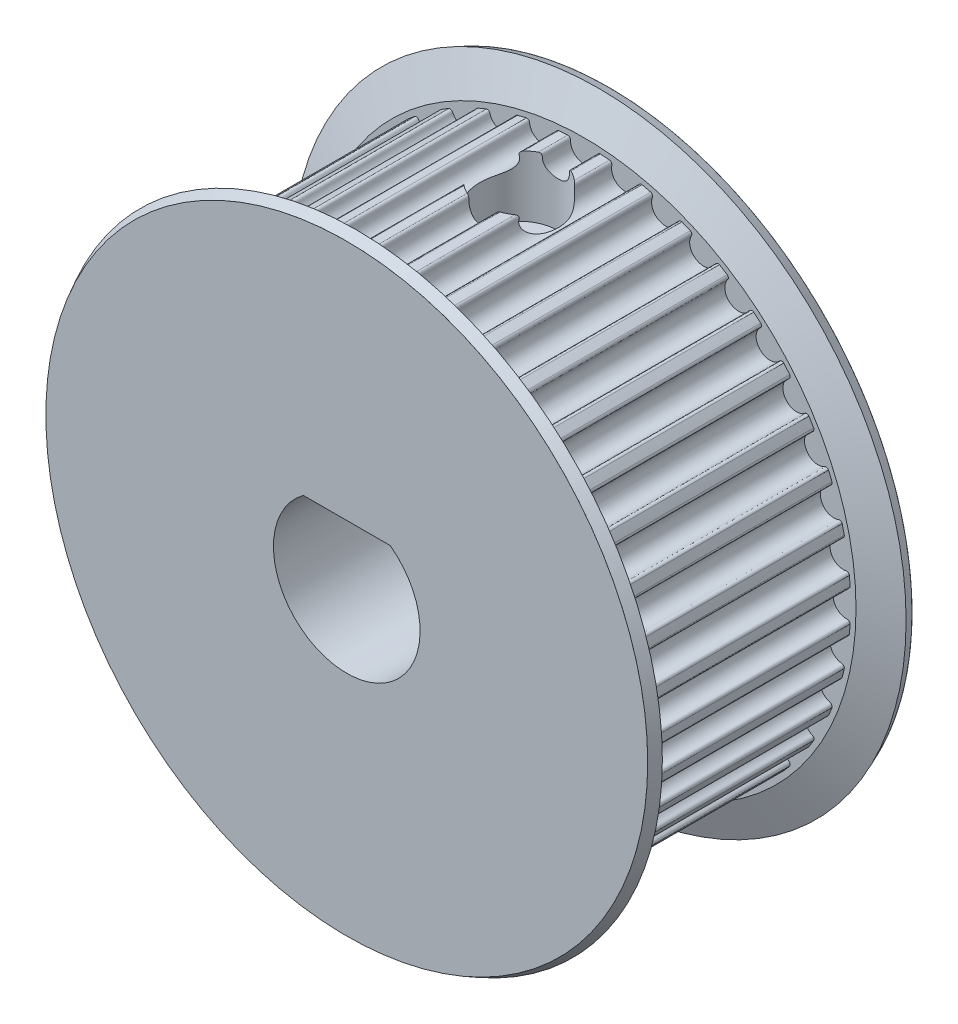
SolidWorks part; units mm, degrees
ref_plane "前视基准面" through (0, 0, 0) normal (0, 0, 1) x (1, 0, 0)
ref_plane "上视基准面" through (0, 0, 0) normal (0, 1, 0) x (1, 0, 0)
ref_plane "右视基准面" through (0, 0, 0) normal (1, 0, 0) x (0, 0, -1)
ref_axis "基准轴1" through (0, 0, 55) along (0, 0, -1)
sketch "SketchRevolveGearBelt01" plane through (0, 0, 0) normal (1, 0, 0) x (0, 0, -1)
  line L0 (0, 0) -> (1, 0) construction
  line L1 (6.4841, 0) -> (6.4841, 19.0696)
  line L2 (6.4841, 19.0696) -> (5.7191, 19.0696)
  line L3 (5.7191, 19.0696) -> (5.7191, 19.934)
  line L4 (5.7191, 19.934) -> (6.2818, 21.2926)
  line L5 (6.2818, 21.2926) -> (5.5778, 21.5842)
  line L6 (5.5778, 21.5842) -> (4.5477, 19.0972)
  line L7 (4.5477, 19.0972) -> (4.5477, 18.7162)
  line L8 (4.5477, 18.7162) -> (-10.2059, 18.7162)
  line L9 (-10.2059, 18.7162) -> (-10.2059, 19.0972)
  line L10 (-10.2059, 19.0972) -> (-11.4448, 21.4871)
  line L11 (-11.4448, 21.4871) -> (-12.1213, 21.1364)
  line L12 (-12.1213, 21.1364) -> (-11.5585, 20.0508)
  line L13 (-11.5585, 20.0508) -> (-11.5585, 19.1864)
  line L14 (-11.5585, 19.1864) -> (-12.3235, 19.1864)
  line L15 (-12.3235, 19.1864) -> (-12.3235, 0)
  line L16 (-12.3235, 0) -> (6.4841, 0)
  dimension "GearBeltFlange1OutsideLength" = 0.8644
  dimension "GearBeltFlange1X" = 0.5627
  dimension "GearBeltFlange1Y" = 1.3586
  dimension "GearBeltFlangeThickness" = 0.762
  dimension "GearBeltFlangeInside" = 0.381
  dimension "GearBeltOutsideDiameter" = 18.7162
  dimension "GearBeltFlange2X" = 0.5627
  dimension "D1" = 14.7536
  dimension "D2" = 17.2776
  dimension "D3" = 0.765
revolve "GearBelt01" add sketch "SketchRevolveGearBelt01" angle 360 about L0
ref_plane "基准面1" through (0, 0, 2.9197) normal (0, 0, -1) x (-1, 0, 0)
sketch "SketchToothGearBelt01" plane through (0, 0, 2.9197) normal (0, 0, 1) x (1, 0, 0)
  arc A0 (18.6805, 1.158) -> (18.6805, -1.158) centre (0, 0) cw
  spline S0 degree 3 poles (18.6805, -1.158) (18.6811, -1.1476) (18.6808, -1.132) (18.6779, -1.1114) (18.6744, -1.0962) (18.6698, -1.0814) (18.6639, -1.0669) (18.6569, -1.053) (18.6487, -1.0397) (18.6395, -1.0272) (18.6294, -1.0154) (18.6182, -1.0044) (18.6063, -0.9945) (18.5935, -0.9855) (18.5801, -0.9776) (18.5661, -0.9708) (18.5516, -0.9652) (18.5366, -0.9607) (18.5214, -0.9576) (18.5059, -0.9556) (18.4728, -0.9546) (18.4207, -0.9557) (18.3495, -0.953) (18.2773, -0.9442) (18.206, -0.9299) (18.136, -0.91) (18.0678, -0.8847) (18.0018, -0.8541) (17.9384, -0.8184) (17.8779, -0.7779) (17.8209, -0.7328) (17.7675, -0.6834) (17.7182, -0.6299) (17.6732, -0.5727) (17.6329, -0.5122) (17.5974, -0.4487) (17.5669, -0.3826) (17.5418, -0.3143) (17.5221, -0.2443) (17.5079, -0.1729) (17.4993, -0.1007) (17.4974, -0.0476) (17.4975, -0.014) (17.4975, 0) (17.4975, 0.014) (17.4974, 0.0476) (17.4993, 0.1007) (17.5079, 0.1729) (17.5221, 0.2443) (17.5418, 0.3143) (17.5669, 0.3826) (17.5974, 0.4487) (17.6329, 0.5122) (17.6732, 0.5727) (17.7182, 0.6299) (17.7675, 0.6834) (17.8209, 0.7328) (17.8779, 0.7779) (17.9384, 0.8184) (18.0018, 0.8541) (18.0678, 0.8847) (18.136, 0.91) (18.206, 0.9299) (18.2773, 0.9442) (18.3495, 0.953) (18.4207, 0.9557) (18.4728, 0.9546) (18.5059, 0.9556) (18.5214, 0.9576) (18.5366, 0.9607) (18.5516, 0.9652) (18.5661, 0.9708) (18.5801, 0.9776) (18.5935, 0.9855) (18.6063, 0.9945) (18.6182, 1.0044) (18.6294, 1.0154) (18.6395, 1.0272) (18.6487, 1.0397) (18.6569, 1.053) (18.6639, 1.0669) (18.6698, 1.0814) (18.6744, 1.0962) (18.6779, 1.1114) (18.6808, 1.132) (18.6811, 1.1476) (18.6805, 1.158) knots 0 0 0 0 0.008364 0.012546 0.016728 0.02091 0.025092 0.029274 0.033456 0.037638 0.04182 0.046002 0.050184 0.054366 0.058548 0.062731 0.066913 0.071095 0.075277 0.079459 0.083641 0.101942 0.121469 0.140996 0.160522 0.180049 0.199576 0.219103 0.238629 0.258156 0.277683 0.29721 0.316736 0.336263 0.35579 0.375316 0.394843 0.41437 0.433897 0.453423 0.47295 0.492477 0.496238 0.5 0.503762 0.507523 0.52705 0.546577 0.566103 0.58563 0.605157 0.624684 0.64421 0.663737 0.683264 0.70279 0.722317 0.741844 0.761371 0.780897 0.800424 0.819951 0.839478 0.859004 0.878531 0.898058 0.916359 0.920541 0.924723 0.928905 0.933087 0.937269 0.941452 0.945634 0.949816 0.953998 0.95818 0.962362 0.966544 0.970726 0.974908 0.97909 0.983272 0.987454 0.991636 1 1 1 1
extrude "ToothExtrudeCutGearBelt01" cut sketch "SketchToothGearBelt01" against normal up to surface and the other way up to surface up to face at (18.7162, 0, -4.5477) other way up to face at (19.0972, 0, 10.2059)
pattern_circular "PatternGearBelt01" count 40 every 9 about axis through (0, 0, 55) along (0, 0, -1) of "ToothExtrudeCutGearBelt01"
sketch "BoreRevolveSketch" plane through (0, 0, 0) normal (1, 0, 0) x (0, 0, -1)
  line L0 (0, 0) -> (1, 0) construction
  line L1 (-18.4604, 0) -> (9.5437, 0)
  line L2 (9.5437, 0) -> (9.5437, 6.35)
  line L3 (9.5437, 6.35) -> (-18.4604, 6.35)
  line L4 (-18.4604, 6.35) -> (-18.4604, 0)
  line L5 (-55, 0) -> (55, 0) construction
  point P6 (-18.4604, 0)
  point P7 (9.5437, 0)
  dimension "TaperSide1" = 6.35
  dimension "TaperSide2" = 6.35
revolve "BoreRevolveCut" cut sketch "BoreRevolveSketch" angle 360 about L0
sketch "AuxiliarySketchGearBelt01" plane through (0, 0, 0) normal (0, 0, 1) x (1, 0, 0)
  circle A0 centre (0, 0) radius 19.0972 construction
  dimension "PitchDiameter" = 38.1944
sketch "草图1" plane through (0, 0, 12.3235) normal (0, 0, 1) x (1, 0, 0)
  circle A0 centre (0, 0) radius 12.15
  dimension "D1" = 24.3
sketch "草图2" plane through (0, 0, 12.3235) normal (0, 0, 1) x (1, 0, 0)
  circle A0 centre (0, 0) radius 22.5
  dimension "D1" = 45
sketch "草图3" plane through (0, 0, -6.4841) normal (0, 0, -1) x (-1, 0, 0)
  line L0 (0, 0) -> (29.6693, 0)
ref_plane "基准面2" through (0, 0, 0) normal (0, -1, 0) x (-1, 0, 0)
sketch "草图4" plane through (0, 0, 0) normal (0, -1, 0) x (-1, 0, 0)
  line L0 (0, -55) -> (0, 55) construction
  line L1 (6.35, 6.4841) -> (-6.35, 6.4841) construction
  circle A0 centre (0, -0.0159) radius 1.5
  dimension "D1" = 3
  dimension "D2" = 6.5
extrude "切除-拉伸1" cut sketch "草图4" against normal blind 35
sketch "草图5" plane through (0, 0, -6.4841) normal (0, 0, -1) x (-1, 0, 0)
  line L0 (-8.3829, 6.35) -> (8.0372, 6.35)
  circle A0 centre (0, 0) radius 6.35 construction
ref_plane "基准面3" through (0, 6.35, 0) normal (0, -1, 0) x (-1, 0, 0)
ref_plane "基准面4" through (0, 14.35, 0) normal (0, -1, 0) x (-1, 0, 0)
sketch "草图7" plane through (0, 14.35, 0) normal (0, -1, 0) x (-1, 0, 0)
  circle A0 centre (0, -0.0159) radius 2.75
  dimension "D1" = 5.5
extrude "切除-拉伸2" cut sketch "草图7" against normal blind 35
sketch "草图8" plane through (0, 0, 12.3235) normal (0, 0, 1) x (1, 0, 0)
  circle A0 centre (0, 0) radius 21.1364
  circle A1 centre (0, 0) radius 19.1864
extrude "凸台-拉伸1" add sketch "草图8" against normal up to surface (0.2023 mm away) up to face at (20.0508, 0, 11.5585)
sketch "草图9" plane through (0, 0, -6.4841) normal (0, 0, -1) x (-1, 0, 0)
  circle A0 centre (0, 0) radius 21.2926
extrude "凸台-拉伸2" add sketch "草图9" against normal up to surface (0.2023 mm away) up to face at (21.2926, 0, -6.2818)
sketch "草图10" plane through (0, 0, 12.3235) normal (0, 0, 1) x (1, 0, 0)
  circle A0 centre (0, 0) radius 6.35
extrude "切除-拉伸3" cut sketch "草图10" against normal blind 35
sketch "草图11" plane through (0, 0, 12.3235) normal (0, 0, 1) x (1, 0, 0)
  line L0 (-4.8062, 4.15) -> (4.8062, 4.15)
  line L2 (-23.4218, 0) -> (23.4218, 0) construction
  circle A1 centre (0, 0) radius 5.15
  circle A2 centre (0, 0) radius 6.35 construction
  circle M2 centre (0, 0) radius 6.35
  dimension "D2" = 10.3
  dimension "D1" = 4.15
extrude "凸台-拉伸3" add sketch "草图11" against normal up to surface (18.8076 mm away) contours A1 L0 M2 | L0 A1 | A1 L0 M2 region at (0, 5.2383, 12.3235) region at (-3.9279, 3.9852, 12.3235) region at (0, 4.5535, 12.3235) up to face at (6.35, 0, -6.4841)
sketch "草图12" plane through (0, 14.35, 0) normal (0, 1, 0) x (1, 0, 0)
  circle A0 centre (0, 0) radius 1.4841
extrude "切除-拉伸4" cut sketch "草图12" against normal up to surface (10.2 mm away) up to face at (0, 4.15, 2.9197)
sketch "草图13" plane through (0, 0, 12.3235) normal (0, 0, 1) x (1, 0, 0)
  circle A0 centre (0, 0) radius 21.4871
extrude "切除-拉伸5" cut sketch "草图13" against normal blind 0.2
mirror "镜向2" about plane through (0, 0, 2.9197) normal (0, 0, -1) of "切除-拉伸5"
